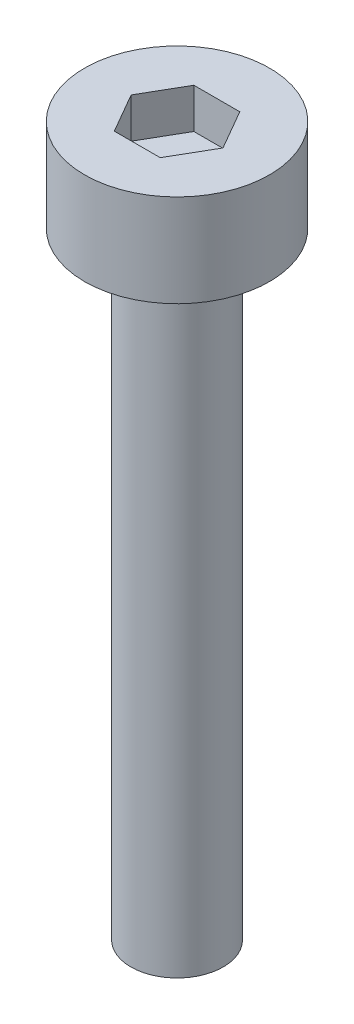
SolidWorks part; units mm, degrees
ref_plane "Front Plane" through (0, 0, 0) normal (0, 0, 1) x (1, 0, 0)
ref_plane "Top Plane" through (0, 0, 0) normal (0, 1, 0) x (1, 0, 0)
ref_plane "Right Plane" through (0, 0, 0) normal (1, 0, 0) x (0, 0, -1)
sketch "Sketch1" plane through (0, 0, 0) normal (0, 1, 0) x (1, 0, 0)
  circle A0 centre (0, 0) radius 1.5
  dimension "D1" = 3
extrude "ScrewShaft" add sketch "Sketch1" along normal blind 20
sketch "Sketch2" plane through (0, 20, 0) normal (0, 1, 0) x (1, 0, 0)
  circle A0 centre (0, 0) radius 3
  dimension "D1" = 6
extrude "Boss-Extrude2" add sketch "Sketch2" along normal blind 3
sketch "Sketch3" plane through (0, 23, 0) normal (0, 1, 0) x (1, 0, 0)
  line L0 (0, 0) -> (0, 1.29) construction
  line L1 (1.4896, 0) -> (0.7448, 1.29)
  line L2 (0.7448, 1.29) -> (-0.7448, 1.29)
  line L3 (-0.7448, 1.29) -> (-1.4896, 0)
  line L4 (-1.4896, 0) -> (-0.7448, -1.29)
  line L5 (-0.7448, -1.29) -> (0.7448, -1.29)
  line L6 (0.7448, -1.29) -> (1.4896, 0)
  circle A0 centre (0, 0) radius 1.29 construction
  dimension "D1" = 2.58
extrude "Cut-Extrude1" cut sketch "Sketch3" against normal blind 1.3
equation "\"X-ROD-SPACING\"=45"
equation "\"Y-ROD-SPACING\"=75"
equation "\"Z-ROD-SPACING\"=17.5"
equation "\"Y-BED-OFFSET\"=2"
equation "\"Y-BED-ROD-INSET\"=3.5"
equation "\"T-SLOT-NUT-FILLET-RADIUS\"=0.5"
equation "\"T-SLOT-SCREW-SHAFT-RADIUS\"=1.55"
equation "\"T-SLOT-SCREW-SHAFT-CUTOUT-LENGTH\"=11"
equation "\"T-SLOT-NUT-DEPTH\"=3.5"
equation "\"T-SLOT-NUT-WIDTH\"=2.85"
equation "\"T-SLOT-NUT-END-DISTANCE\"=8"
equation "\"ACRYLIC-THICKNESS\"=10"
equation "\"ACRYLIC-THICKNESS2\"=4.5"
equation "\"ACRYLIC-TAB-CUTOUT-SIZE\"=\"ACRYLIC-THICKNESS\"+\"ACRYLIC-TAB-TOLERANCE\"*2"
equation "\"ACRYLIC-TAB-WIDTH\"=\"ACRYLIC-THICKNESS\""
equation "\"ACRYLIC-M3-HOLE\"=2.9"
equation "\"SMOOTHROD-CAP-SCREW-DISTANCE\"=20"
equation "\"FRAME-WIDTH-INNER\"=370"
equation "\"NEMA17-HOLE-SPACING\"=31"
equation "\"NEMA17-CENTRAL-CUTOUT\"=22.5"
equation "\"Z-BRACKET-REACH\"=57"
equation "\"TOP-BRACKET-SPACING\"=40"
equation "\"SMOOTHROD-X-LENGTH\"=350"
equation "\"SMOOTHROD-Y-LENGTH\"=350"
equation "\"SMOOTHROD-Z-LENGTH\"=350"
equation "\"SMOOTHROD-TIGHTENING-HEADROOM\"=.25"
equation "\"LEADSCREW-Z-LENGTH\"=300"
equation "\"SCREW-LENGTH-FRAME\"=\"ACRYLIC-THICKNESS\" + 10"
equation "\"SCREW-HEAD-RADIUS\"=6"
equation "\"PRINTED-X-SMOOTHROD-DIAMETER\"=8.8"
equation "\"PRINTED-X-SMOOTHROD-CUTOUT\"=10"
equation "\"PRINTED-X-BASE-HEIGHT\"=10"
equation "\"PRINTED-LM8UU-CUTOUT-SIZE\"=15.5"
equation "\"PRINTED-LM8UU-CUTOUT-LENGTH\"=24.5"
equation "\"PRINTED-X-IDLER-HEIGHT\"=16"
equation "\"PSU-MOUNTING-WIDTH\"=95"
equation "\"PSU-MOUNTING-HEIGHT\"=177"
equation "\"D1@ScrewShaft\"=\"SCREW-LENGTH-FRAME\""
equation "\"D1@Sketch2\"=\"SCREW-HEAD-RADIUS\""
